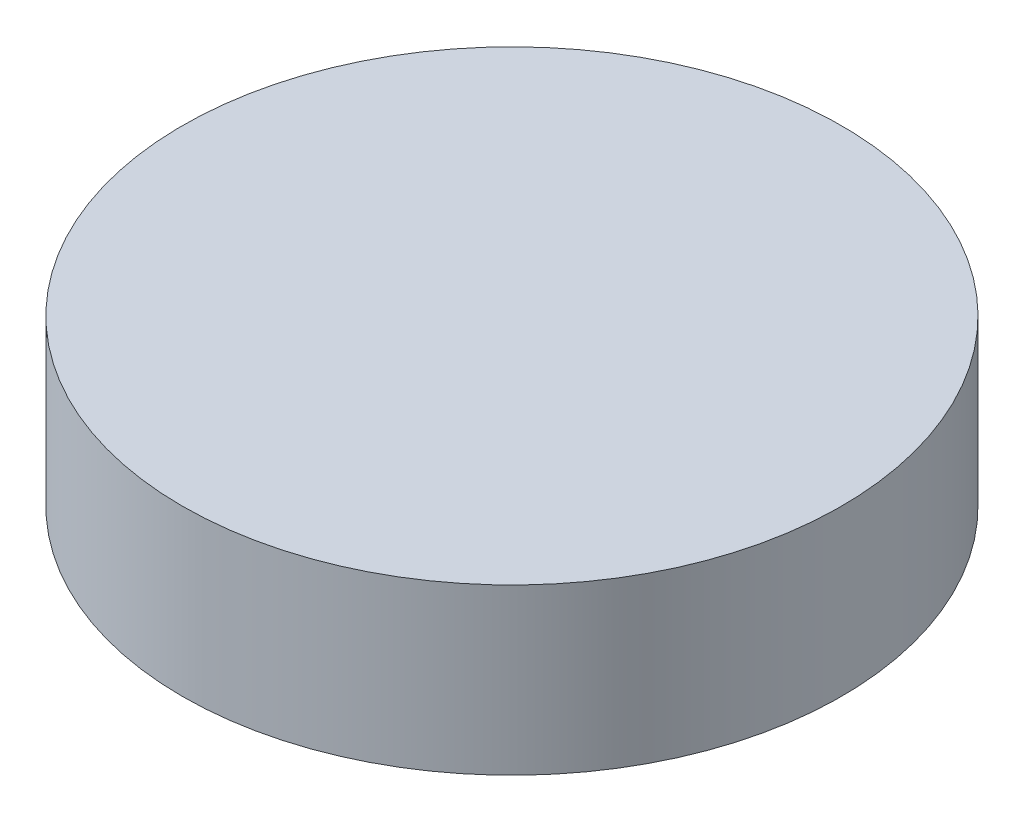
SolidWorks part; units mm, degrees
ref_plane "Front Plane" through (0, 0, 0) normal (0, 0, 1) x (1, 0, 0)
ref_plane "Top Plane" through (0, 0, 0) normal (0, 1, 0) x (1, 0, 0)
ref_plane "Right Plane" through (0, 0, 0) normal (1, 0, 0) x (0, 0, -1)
sketch "Sketch4" plane through (0, 0, 0) normal (0, 1, 0) x (1, 0, 0)
  circle A0 centre (0, 0) radius 10.16
  dimension "D1" = 20.32
extrude "Boss-Extrude1" add sketch "Sketch4" along normal blind 2.54 and the other way blind 2.54
